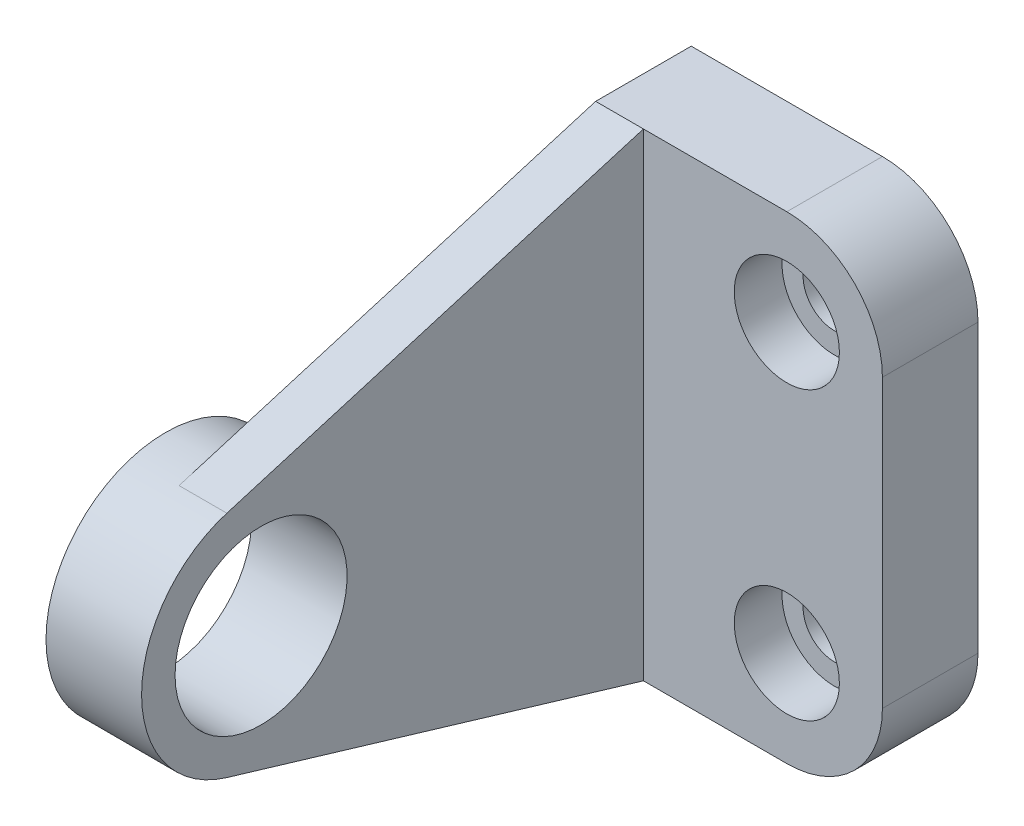
SolidWorks part; units mm, degrees
ref_plane "前视基准面" through (0, 0, 0) normal (0, 0, 1) x (1, 0, 0)
ref_plane "上视基准面" through (0, 0, 0) normal (0, 1, 0) x (1, 0, 0)
ref_plane "右视基准面" through (0, 0, 0) normal (1, 0, 0) x (0, 0, -1)
sketch "草图1" plane through (0, 0, 0) normal (0, 0, 1) x (1, 0, 0)
  line L1 (-15, 25) -> (15, 25)
  line L2 (-15, 25) -> (-15, -25)
  line L3 (-15, -25) -> (15, -25)
  line L4 (15, 25) -> (15, -25)
  line L5 (0, -25) -> (0, 25) construction
  line L6 (-15, 0) -> (15, 0) construction
  point P0 (0, 0)
  dimension "D1" = 30
  dimension "D2" = 50
extrude "凸台-拉伸2" add sketch "草图1" along normal blind 10
sketch "草图2" plane through (-15, 0, 0) normal (-1, 0, 0) x (0, 0, 1)
  line L0 (10, -25) -> (53.5791, -11.9766)
  line L1 (10, 25) -> (53.5791, 11.9766)
  circle A0 centre (50, 0) radius 12.5
  circle A2 centre (50, 0) radius 9
  line M3 (10, -25) -> (10, 25)
  dimension "D1" = 25
  dimension "D3" = 18
  dimension "D2" = 50
extrude "凸台-拉伸3" add sketch "草图2" against normal blind 5 contours A0 L1 L0 M3 region at (-15, 0, 24.7041)
extrude "凸台-拉伸4" add sketch "草图2<3>" along normal blind 5 and the other way blind 5 contours A0 A2 region at (-15, -7.2558, 59.7412)
sketch "草图2<3>" plane through (-15, 0, 0) normal (-1, 0, 0) x (0, 0, 1) same geometry as "草图2"
fillet "圆角1" radius 10 2 edges at (15, 25, 5) (15, -25, 5)
hole_wizard "打孔尺寸(%根据)内六角圆柱头螺钉的类型1" positions "草图3" profile "草图5" counterbore size "M6" standard "GB" end condition through all
sketch "草图3" plane through (0, 0, 10) normal (0, 0, 1) x (1, 0, 0)
  point P0 (5, -15)
  point P3 (5, 15)
sketch "草图5" plane through (5, -15, 10) normal (1, 0, 0) x (0, -1, 0)
  line L0 (0, 0) -> (0, 10)
  line L1 (0, 10) -> (3.3, 10)
  line L3 (3.3, 10) -> (3.3, 5)
  line L4 (3.3, 5) -> (5.5, 5)
  line L5 (5.5, 5) -> (5.5, 0)
  line L7 (5.5, 0) -> (0, 0)
  line L11 (0, -6.35) -> (0, 107.95) construction
  dimension "通孔孔直径" = 6.6
  dimension "通孔孔深度" = 10
  dimension "柱形沉头孔直径" = 11
  dimension "柱形沉头孔深度" = 5
move or copy body "实体-移动/复制1" [suppressed] bodies to move or copy 110 copy no rotation origin (-8.6336, -12.8593, 10.5433) rotation axis (0.244, 0.5116, 0.8238) rotation angle 60.139
